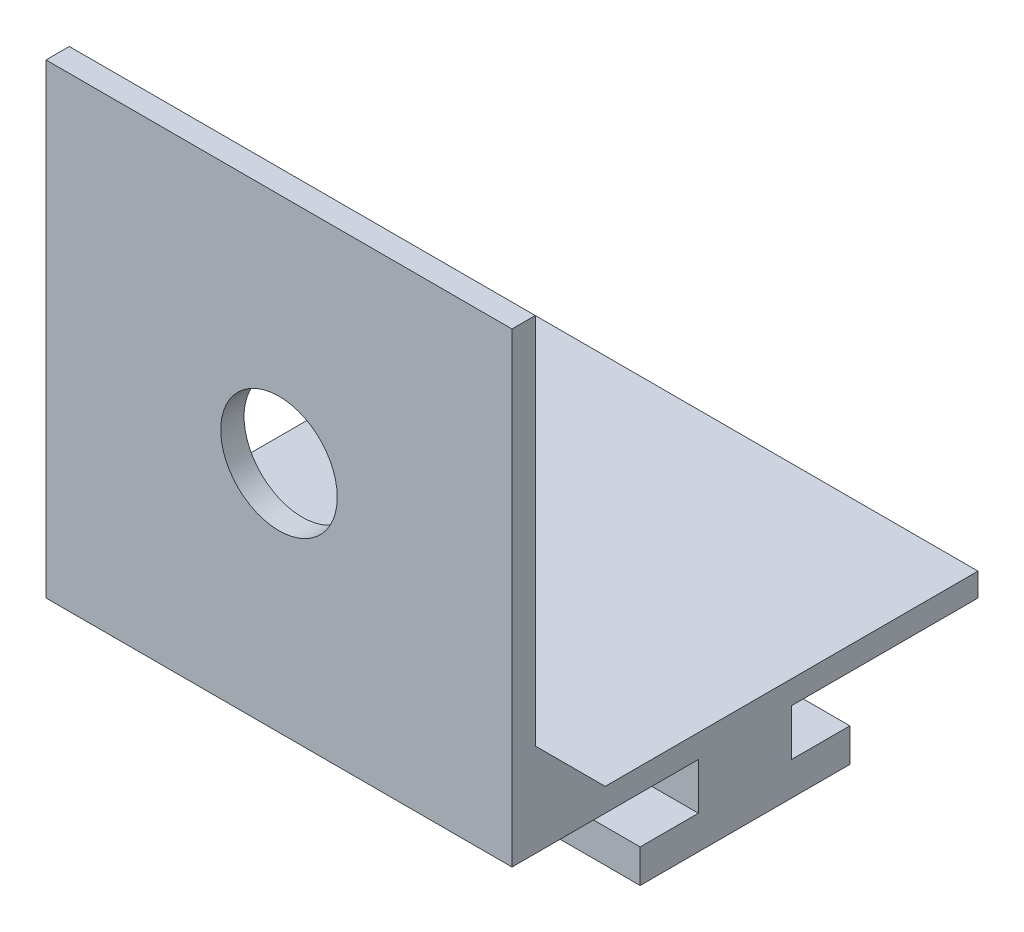
SolidWorks part; units mm, degrees
ref_plane "Front Plane" through (0, 0, 0) normal (0, 0, 1) x (1, 0, 0)
ref_plane "Top Plane" through (0, 0, 0) normal (0, 1, 0) x (1, 0, 0)
ref_plane "Right Plane" through (0, 0, 0) normal (1, 0, 0) x (0, 0, -1)
sketch "Sketch1" plane through (0, 0, 0) normal (0, 1, 0) x (1, 0, 0)
  line L1 (10, 10) -> (-10, 10)
  line L2 (10, 10) -> (10, -10)
  line L3 (10, -10) -> (-10, -10)
  line L4 (-10, 10) -> (-10, -10)
  line L5 (10, 10) -> (-10, -10) construction
  line L6 (10, -10) -> (-10, 10) construction
  point P0 (0, 0)
  dimension "D1" = 20
  dimension "D2" = 20
extrude "Boss-Extrude1" add sketch "Sketch1" along normal blind 1
sketch "Sketch2" plane through (0, 0, 10) normal (0, 0, 1) x (1, 0, 0)
  line L1 (-10, 0) -> (10, 0)
  line L2 (-10, 0) -> (-10, 20)
  line L3 (-10, 20) -> (10, 20)
  line L4 (10, 0) -> (10, 20)
  circle A0 centre (0, 10) radius 2.5
extrude "Boss-Extrude2" add sketch "Sketch2" against normal blind 1
sketch "Sketch3" plane through (10, 0, 0) normal (1, 0, 0) x (0, 0, -1)
  line L0 (-9, 4) -> (-6, 1)
  line L3 (-6, 1) -> (-9, 1)
  line L4 (-9, 1) -> (-9, 4)
  line L5 (-9, 1) -> (10, 1) construction
extrude "Boss-Extrude3" add sketch "Sketch3" against normal blind 20
extrude "Boss-Extrude4" add sketch "Sketch3<2>" against normal blind 1 from offset 19 offset against normal yes
sketch "Sketch3<2>" plane through (10, 0, 0) normal (1, 0, 0) x (0, 0, -1) same geometry as "Sketch3"
sketch "Sketch4" plane through (10, 0, 0) normal (1, 0, 0) x (0, 0, -1)
  line L0 (-2, 0) -> (-2, -2)
  line L1 (-10, 0) -> (10, 0) construction
  line L2 (-2, -2) -> (-4.5, -2)
  line L3 (-4.5, -2) -> (-4.5, -3.4361)
  line L4 (-4.5, -3.4361) -> (4.5, -3.4361)
  line L5 (4.5, -3.4361) -> (4.5, -2)
  line L6 (4.5, -2) -> (2, -2)
  line L7 (2, -2) -> (2, 0)
  line L8 (-2, 0) -> (2, 0)
  dimension "D1" = 2
  dimension "D2" = 2
  dimension "D4" = 2.5
extrude "Boss-Extrude5" add sketch "Sketch4" against normal blind 20 contours L2 L3 L4 L5 L6 L7 L8 L0
